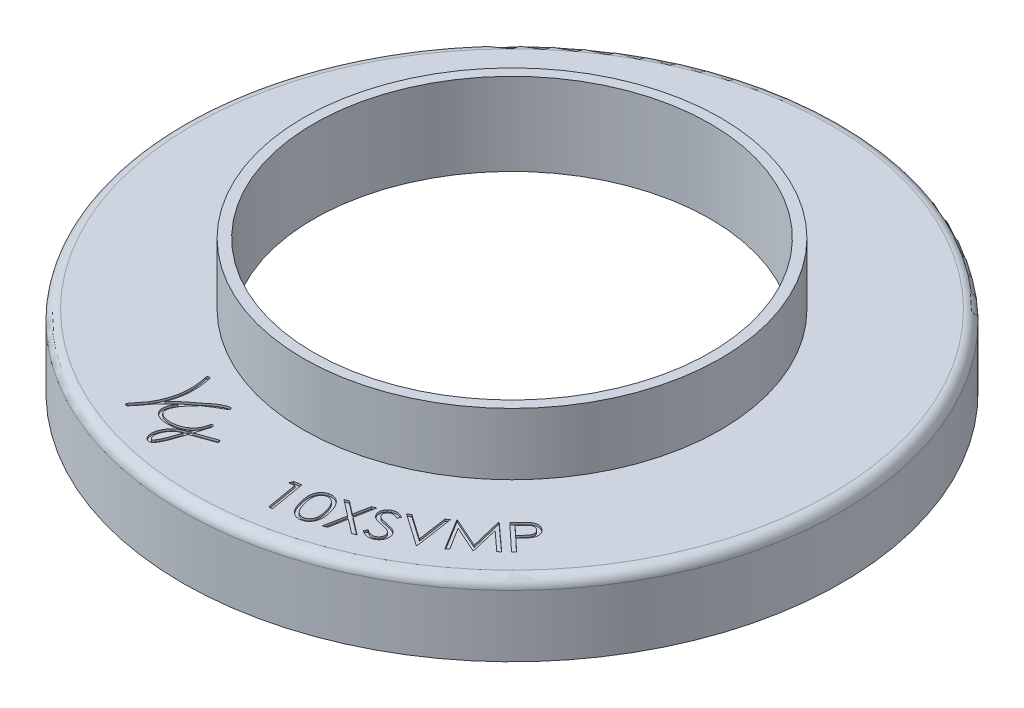
SolidWorks part; units mm, degrees
material "BioMed Black"
ref_plane "Front Plane" through (0, 0, 0) normal (0, 0, 1) x (1, 0, 0)
ref_plane "Top Plane" through (0, 0, 0) normal (0, 1, 0) x (1, 0, 0)
ref_plane "Right Plane" through (0, 0, 0) normal (1, 0, 0) x (0, 0, -1)
sketch "Sketch1" plane through (0, 0, 0) normal (0, 1, 0) x (1, 0, 0)
  circle A0 centre (0, 0) radius 32
  dimension "D1" = 64
extrude "Boss-Extrude1" add sketch "Sketch1" along normal blind 1
sketch "Sketch2" plane through (0, 0, 0) normal (0, -1, 0) x (1, 0, 0)
  circle A0 centre (0, 0) radius 19.25
  dimension "D1" = 38.5
extrude "Cut-Extrude1" cut sketch "Sketch2" against normal through all
sketch "Sketch3" plane through (0, 0, 0) normal (0, -1, 0) x (1, 0, 0)
  circle A0 centre (0, 0) radius 32
  circle A1 centre (0, 0) radius 31.5
  circle A3 centre (0, 0) radius 32 construction
  dimension "D1" = 0.5
extrude "Boss-Extrude2" add sketch "Sketch3" along normal blind 6
sketch "Sketch4" plane through (0, 1, 0) normal (0, 1, 0) x (1, 0, 0)
  circle A0 centre (0, 0) radius 19.25
  circle A1 centre (0, 0) radius 20.25
  dimension "D1" = 1
extrude "Boss-Extrude3" add sketch "Sketch4" along normal blind 6 and the other way blind 2
fillet "Fillet1" radius 1 1 edges at (0, 1, 32)
sketch "Sketch5" plane through (0, 1, 0) normal (0, 1, 0) x (-1, 0, 0)
  arc A2 (10.5475, 26.744) -> (10.7697, 26.5362) centre (10.6586, 26.6401) cw
  arc A3 (8.8761, 20.4894) -> (9.1721, 20.5598) centre (9.0241, 20.5246) ccw
  arc A4 (10.5343, 26.7277) -> (10.7829, 26.5524) centre (10.6586, 26.6401) cw
  arc A5 (5.3559, 22.193) -> (5.4967, 21.9233) centre (5.4263, 22.0581) ccw
  arc A6 (5.9185, 26.1576) -> (5.8121, 26.4426) centre (5.8653, 26.3001) cw
  arc A7 (4.6798, 24.431) -> (4.9727, 24.3487) centre (4.8263, 24.3898) ccw
  arc A8 (3.2789, 25.2131) -> (3.1764, 25.4995) centre (3.2277, 25.3563) cw
  arc A9 (5.9166, 26.1569) -> (5.8141, 26.4433) centre (5.8653, 26.3001) ccw
  arc A10 (5.4318, 21.9061) -> (5.4208, 22.2101) centre (5.4263, 22.0581) cw
  arc A11 (4.6751, 24.4067) -> (4.9774, 24.3729) centre (4.8263, 24.3898) ccw
  spline S0 degree 2 poles (10.6586, 26.6401) (8.1956, 24.0072) (9.0241, 20.5246) knots 0 0 0 1 1 1 construction
  spline S1 degree 2 poles (10.6586, 26.6401) (8.5937, 23.7116) (5.4263, 22.0581) knots 0 0 0 1 1 1 construction
  spline S2 degree 3 poles (5.4263, 22.0581) (6.3799, 22.0926) (10.2082, 25.6921) (6.3521, 26.4783) (5.0792, 25.3888) (4.852, 24.5685) (4.8316, 24.4373) (4.8263, 24.3898) knots 0 0 0 0 0.530866 0.72538 0.957095 0.984557 1 1 1 1 construction
  spline S3 degree 3 poles (5.8653, 26.3001) (6.5714, 26.5635) (7.2534, 27.8751) (6.3675, 28.9607) (5.8422, 28.0063) (4.8263, 24.3898) knots 0 0 0 0 0.452994 0.552994 1 1 1 1 construction
  spline S4 degree 1 poles (3.2277, 25.3563) (5.8653, 26.3001) knots 0 0 1 1 construction
  spline S11 degree 2 poles (10.5475, 26.744) (8.0312, 24.0514) (8.8761, 20.4894) knots 0 0 0 1 1 1
  spline S13 degree 2 poles (10.7697, 26.5362) (8.3599, 23.963) (9.1721, 20.5598) knots 0 0 0 1 1 1
  spline S15 degree 2 poles (10.5343, 26.7277) (8.4907, 23.8292) (5.3559, 22.193) knots 0 0 0 1 1 1
  spline S17 degree 2 poles (10.7829, 26.5524) (8.6968, 23.594) (5.4967, 21.9233) knots 0 0 0 1 1 1
  spline S19 degree 3 poles (5.9185, 26.1576) (6.3717, 26.3267) (6.8984, 26.9544) (7.1709, 27.8934) (7.0135, 28.4415) (6.7357, 28.709) (6.3154, 28.761) (6.0293, 28.3908) (5.7014, 27.6737) (5.4175, 26.8922) (5.1383, 26.0114) (4.8892, 25.1689) (4.7472, 24.6708) (4.6798, 24.431) knots 0 0 0 0 0.25 0.375 0.5 0.5625 0.625 0.75 0.8125 0.875 0.9375 0.96875 1 1 1 1
  spline S21 degree 3 poles (5.8121, 26.4426) (5.9954, 26.511) (6.3045, 26.7422) (6.6925, 27.3191) (6.8485, 27.9236) (6.7424, 28.2885) (6.5593, 28.429) (6.5334, 28.4322) (6.4149, 28.369) (6.2188, 28.0773) (5.985, 27.5615) (5.7062, 26.7964) (5.4293, 25.9226) (5.1814, 25.0843) (5.0399, 24.5877) (4.9727, 24.3487) knots 0 0 0 0 0.125 0.25 0.375 0.5 0.5625 0.625 0.6875 0.75 0.8125 0.875 0.9375 0.96875 1 1 1 1
  spline S23 degree 1 poles (3.2789, 25.2131) (5.9166, 26.1569) knots 0 0 1 1
  spline S25 degree 1 poles (3.1764, 25.4995) (5.8141, 26.4433) knots 0 0 1 1
  spline S27 degree 3 poles (5.4318, 21.9061) (5.5912, 21.9119) (5.8735, 22.0048) (6.5962, 22.4138) (7.5826, 23.2586) (8.5251, 24.4716) (8.7986, 25.4706) (8.3112, 26.0811) (7.5144, 26.3909) (5.7553, 26.3608) (4.7664, 25.2231) (4.6751, 24.4067) knots 0 0 0 0 0.0625 0.125 0.25 0.375 0.5 0.5625 0.625 0.75 1 1 1 1
  spline S29 degree 3 poles (5.4208, 22.2101) (5.4718, 22.212) (5.559, 22.2284) (5.833, 22.3277) (6.2411, 22.5633) (6.79, 22.9827) (7.5131, 23.6633) (8.2711, 24.6485) (8.4385, 25.4407) (8.147, 25.8028) (7.478, 26.0869) (5.8933, 26.0473) (5.0564, 25.0785) (4.9774, 24.3729) knots 0 0 0 0 0.03125 0.0625 0.125 0.1875 0.25 0.375 0.5 0.5625 0.625 0.75 1 1 1 1
extrude "Tag" cut sketch "Sketch5" against normal blind 0.2 contours S19 A7 S21 A6 | S27 A11 S29 A10 | S25 A9 S23 A8 | S15 A5 S17 A4 | S11 A3 S13 A2
sketch "Sketch6" plane through (0, 1, 0) normal (0, 1, 0) x (1, 0, 0)
  arc A0 (3.578, -28.6314) -> (27.1893, -9.659) centre (0, 0) ccw construction
  text T0 "10XSVMP"
extrude "Compatibility text" cut sketch "Sketch6" against normal blind 0.2
